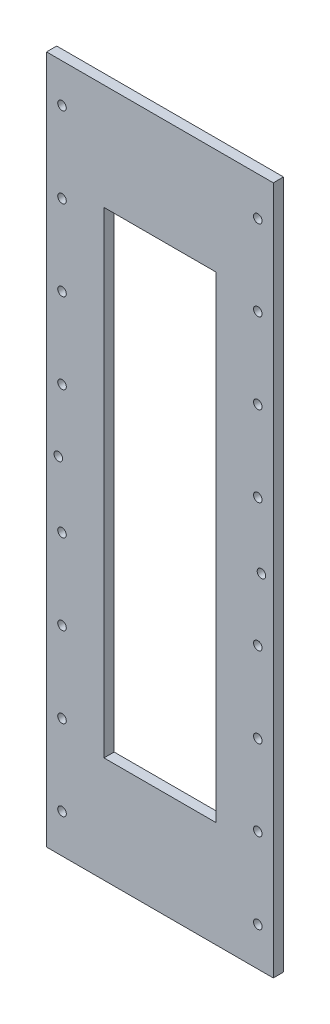
SolidWorks part; units mm, degrees
ref_plane "Front Plane" through (0, 0, 0) normal (0, 0, 1) x (1, 0, 0)
ref_plane "Top Plane" through (0, 0, 0) normal (0, 1, 0) x (1, 0, 0)
ref_plane "Right Plane" through (0, 0, 0) normal (1, 0, 0) x (0, 0, -1)
sketch "Sketch1" plane through (0, 0, 0.1) normal (0, 0, 1) x (1, 0, 0)
  line L0 (-40.45, -31.4857) -> (-40.45, -150) construction
  line L1 (-27.45, 117) -> (27.45, 117)
  line L2 (-30.45, 120) -> (30.45, 120)
  line L3 (-30.45, 120) -> (-30.45, -120)
  line L4 (-30.45, -120) -> (30.45, -120)
  line L5 (30.45, 120) -> (30.45, -120)
  line L6 (27.45, 117) -> (27.45, -117)
  line L7 (-27.45, -117) -> (27.45, -117)
  line L8 (0, -161.5) -> (0, -169)
  line L9 (-55.65, 169) -> (55.65, 169)
  line L10 (-55.65, 169) -> (-55.65, -169)
  line L11 (-55.65, -169) -> (55.65, -169)
  line L12 (55.65, 169) -> (55.65, -169)
  line L14 (67.25, -161.5) -> (-67.25, -161.5) construction
  line L15 (-27.45, 117) -> (-27.45, -117)
  line L16 (0, 169) -> (0, 161.5) construction
  line L19 (0, 169) -> (0, 176.5) construction
  line L22 (82.25, 176.5) -> (-82.25, 176.5) construction
  line L23 (-67.25, 161.5) -> (67.25, 161.5) construction
  line L32 (0, -176.5) -> (0, -169)
  line L34 (-82.25, -176.5) -> (82.25, -176.5) construction
  circle A0 centre (-48.05, -150) radius 2.1 construction
  circle A1 centre (48.05, -150) radius 2.1 construction
  circle A2 centre (49.85, 0) radius 2.1
  circle A3 centre (48.05, -70.9904) radius 2.1
  circle A4 centre (48.05, -110.4952) radius 2.1
  circle A5 centre (48.05, -150) radius 2.1
  circle A6 centre (-48.05, -150) radius 2.1
  circle A7 centre (-48.05, -110.4952) radius 2.1
  circle A8 centre (-48.05, -70.9904) radius 2.1
  circle A9 centre (-48.05, 150) radius 2.1 construction
  circle A23 centre (-48.05, 150) radius 2.1
  circle A24 centre (48.05, 150) radius 2.1
  circle A25 centre (48.05, 110.4952) radius 2.1
  circle A26 centre (-48.05, 110.4952) radius 2.1
  circle A27 centre (-48.05, 70.9904) radius 2.1
  circle A28 centre (-48.05, 31.4857) radius 2.1
  circle A29 centre (48.05, 70.9904) radius 2.1
  circle A30 centre (48.05, 31.4857) radius 2.1
  circle A31 centre (-49.85, 0) radius 2.1
  circle A64 centre (-48.05, -31.4857) radius 2.1
  circle A65 centre (48.05, -31.4857) radius 2.1
  line M30 (10.45, -45) -> (30.45, -45)
  line M31 (30.45, -45) -> (30.45, -103)
  line M32 (30.45, -103) -> (10.45, -103)
  line M33 (-10.45, -103) -> (-30.45, -103)
  line M34 (-30.45, -103) -> (-30.45, -45)
  line M35 (-30.45, -45) -> (-10.45, -45)
  line M38 (-10.45, 45) -> (-30.45, 45)
  line M39 (-30.45, 45) -> (-30.45, 103)
  line M40 (-30.45, 103) -> (-10.45, 103)
  line M41 (10.45, 103) -> (30.45, 103)
  line M42 (30.45, 103) -> (30.45, 45)
  line M43 (30.45, 45) -> (10.45, 45)
  arc M45 (-45.6346, -16.16) -> (-41.3067, -23.1285) centre (-50.75, -24.1652) cw
  arc M46 (-41.3067, -23.1285) -> (-45.45, -31.4857) centre (-34.95, -31.4857) ccw
  line M47 (-45.45, -31.4857) -> (-45.45, -150)
  arc M48 (-45.45, -150) -> (-34.95, -160.5) centre (-34.95, -150) ccw
  line M49 (-34.95, -160.5) -> (34.95, -160.5)
  arc M50 (34.95, -160.5) -> (45.45, -150) centre (34.95, -150) ccw
  line M51 (45.45, -150) -> (45.45, -31.4857)
  arc M52 (45.45, -31.4857) -> (41.3067, -23.1285) centre (34.95, -31.4857) ccw
  arc M53 (41.3067, -23.1285) -> (45.6346, -16.16) centre (50.75, -24.1652) cw
  arc M54 (45.6346, -16.16) -> (47.25, -13.2107) centre (43.75, -13.2107) ccw
  line M55 (47.25, -13.2107) -> (47.25, 13.2107)
  arc M56 (47.25, 13.2107) -> (45.6346, 16.16) centre (43.75, 13.2107) ccw
  arc M57 (45.6346, 16.16) -> (41.3067, 23.1285) centre (50.75, 24.1652) cw
  arc M58 (41.3067, 23.1285) -> (45.45, 31.4857) centre (34.95, 31.4857) ccw
  line M59 (45.45, 31.4857) -> (45.45, 150)
  arc M60 (45.45, 150) -> (34.95, 160.5) centre (34.95, 150) ccw
  line M61 (34.95, 160.5) -> (-34.95, 160.5)
  arc M62 (-34.95, 160.5) -> (-45.45, 150) centre (-34.95, 150) ccw
  line M63 (-45.45, 150) -> (-45.45, 31.4857)
  arc M64 (-45.45, 31.4857) -> (-41.3067, 23.1285) centre (-34.95, 31.4857) ccw
  arc M65 (-41.3067, 23.1285) -> (-45.6346, 16.16) centre (-50.75, 24.1652) cw
  arc M66 (-45.6346, 16.16) -> (-47.25, 13.2107) centre (-43.75, 13.2107) ccw
  line M67 (-47.25, 13.2107) -> (-47.25, -13.2107)
  arc M68 (-47.25, -13.2107) -> (-45.6346, -16.16) centre (-43.75, -13.2107) ccw
  dimension "D1" = 7.6
  dimension "D2" = 7.6
  dimension "D3" = 7.6
  dimension "D5" = 180
  dimension "D4" = 3
sketch "Sketch2" plane through (0, 0, 0.1) normal (0, 0, 1) x (1, 0, 0)
  line L12 (45.45, 31.4857) -> (45.45, 150)
  line L14 (45.45, 31.4857) -> (45.45, 150)
  line L16 (-45.45, -31.4857) -> (-45.45, -150)
  line L17 (-34.95, -160.5) -> (34.95, -160.5)
  line L18 (45.45, -150) -> (45.45, -31.4857)
  line L19 (47.25, -13.2107) -> (47.25, 13.2107)
  line L24 (-45.45, -31.4857) -> (-45.45, -150)
  line L25 (-34.95, -160.5) -> (34.95, -160.5)
  line L26 (45.45, -150) -> (45.45, -31.4857)
  line L27 (47.25, -13.2107) -> (47.25, 13.2107)
  line L38 (34.95, 160.5) -> (-34.95, 160.5)
  line L39 (34.95, 160.5) -> (-34.95, 160.5)
  line L40 (-45.45, 150) -> (-45.45, 31.4857)
  line L41 (-45.45, 150) -> (-45.45, 31.4857)
  line L42 (-47.25, 13.2107) -> (-47.25, -13.2107)
  line L43 (-47.25, 13.2107) -> (-47.25, -13.2107)
  line L44 (-42.25, 12.4178) -> (-42.25, -12.4178)
  line L45 (-42.25, 12.4178) -> (-42.25, -12.4178)
  line L46 (-40.45, -31.4857) -> (-40.45, -150)
  line L47 (-40.45, -31.4857) -> (-40.45, -150)
  line L56 (-34.95, -155.5) -> (34.95, -155.5)
  line L57 (-34.95, -155.5) -> (34.95, -155.5)
  line L58 (40.45, -150) -> (40.45, -31.4857)
  line L59 (40.45, -150) -> (40.45, -31.4857)
  line L60 (42.25, -12.4178) -> (42.25, 12.4178)
  line L61 (42.25, -12.4178) -> (42.25, 12.4178)
  line L62 (40.45, 31.4857) -> (40.45, 150)
  line L63 (40.45, 31.4857) -> (40.45, 150)
  line L64 (34.95, 155.5) -> (-34.95, 155.5)
  line L65 (34.95, 155.5) -> (-34.95, 155.5)
  line L66 (-40.45, 150) -> (-40.45, 31.4857)
  line L67 (-40.45, 150) -> (-40.45, 31.4857)
  arc A9 (-42.25, 12.4178) -> (-36.3903, 26.1776) centre (-50.75, 24.1652) ccw
  arc A32 (-41.3067, -23.1285) -> (-45.6346, -16.16) centre (-50.75, -24.1652) ccw
  arc A33 (-41.3067, -23.1285) -> (-45.45, -31.4857) centre (-34.95, -31.4857) ccw
  arc A34 (-45.45, -150) -> (-34.95, -160.5) centre (-34.95, -150) ccw
  arc A35 (34.95, -160.5) -> (45.45, -150) centre (34.95, -150) ccw
  arc A36 (45.45, -31.4857) -> (41.3067, -23.1285) centre (34.95, -31.4857) ccw
  arc A37 (45.6346, -16.16) -> (41.3067, -23.1285) centre (50.75, -24.1652) ccw
  arc A38 (45.6346, -16.16) -> (47.25, -13.2107) centre (43.75, -13.2107) ccw
  arc A45 (-42.25, 12.4178) -> (-36.3903, 26.1776) centre (-50.75, 24.1652) ccw
  arc A46 (-36.3903, -26.1776) -> (-42.25, -12.4178) centre (-50.75, -24.1652) ccw
  arc A47 (-47.25, -13.2107) -> (-45.6346, -16.16) centre (-43.75, -13.2107) ccw
  arc A48 (-41.3067, -23.1285) -> (-45.6346, -16.16) centre (-50.75, -24.1652) ccw
  arc A49 (-41.3067, -23.1285) -> (-45.45, -31.4857) centre (-34.95, -31.4857) ccw
  arc A50 (-45.45, -150) -> (-34.95, -160.5) centre (-34.95, -150) ccw
  arc A51 (34.95, -160.5) -> (45.45, -150) centre (34.95, -150) ccw
  arc A52 (45.45, -31.4857) -> (41.3067, -23.1285) centre (34.95, -31.4857) ccw
  arc A53 (45.6346, -16.16) -> (41.3067, -23.1285) centre (50.75, -24.1652) ccw
  arc A54 (45.6346, -16.16) -> (47.25, -13.2107) centre (43.75, -13.2107) ccw
  arc A63 (-47.25, -13.2107) -> (-45.6346, -16.16) centre (-43.75, -13.2107) ccw
  arc A64 (-36.3903, -26.1776) -> (-42.25, -12.4178) centre (-50.75, -24.1652) ccw
  arc A65 (-36.3903, -26.1776) -> (-40.45, -31.4857) centre (-34.95, -31.4857) ccw
  arc A66 (47.25, 13.2107) -> (45.6346, 16.16) centre (43.75, 13.2107) ccw
  arc A67 (47.25, 13.2107) -> (45.6346, 16.16) centre (43.75, 13.2107) ccw
  arc A68 (41.3067, 23.1285) -> (45.6346, 16.16) centre (50.75, 24.1652) ccw
  arc A69 (41.3067, 23.1285) -> (45.6346, 16.16) centre (50.75, 24.1652) ccw
  arc A70 (41.3067, 23.1285) -> (45.45, 31.4857) centre (34.95, 31.4857) ccw
  arc A71 (41.3067, 23.1285) -> (45.45, 31.4857) centre (34.95, 31.4857) ccw
  arc A72 (45.45, 150) -> (34.95, 160.5) centre (34.95, 150) ccw
  arc A73 (45.45, 150) -> (34.95, 160.5) centre (34.95, 150) ccw
  arc A74 (-34.95, 160.5) -> (-45.45, 150) centre (-34.95, 150) ccw
  arc A75 (-34.95, 160.5) -> (-45.45, 150) centre (-34.95, 150) ccw
  arc A76 (-45.45, 31.4857) -> (-41.3067, 23.1285) centre (-34.95, 31.4857) ccw
  arc A77 (-45.45, 31.4857) -> (-41.3067, 23.1285) centre (-34.95, 31.4857) ccw
  arc A78 (-45.6346, 16.16) -> (-41.3067, 23.1285) centre (-50.75, 24.1652) ccw
  arc A79 (-45.6346, 16.16) -> (-41.3067, 23.1285) centre (-50.75, 24.1652) ccw
  arc A80 (-45.6346, 16.16) -> (-47.25, 13.2107) centre (-43.75, 13.2107) ccw
  arc A81 (-45.6346, 16.16) -> (-47.25, 13.2107) centre (-43.75, 13.2107) ccw
  arc A82 (-36.3903, -26.1776) -> (-40.45, -31.4857) centre (-34.95, -31.4857) ccw
  arc A83 (-40.45, -150) -> (-34.95, -155.5) centre (-34.95, -150) ccw
  arc A96 (-40.45, -150) -> (-34.95, -155.5) centre (-34.95, -150) ccw
  arc A97 (34.95, -155.5) -> (40.45, -150) centre (34.95, -150) ccw
  arc A98 (34.95, -155.5) -> (40.45, -150) centre (34.95, -150) ccw
  arc A99 (40.45, -31.4857) -> (36.3903, -26.1776) centre (34.95, -31.4857) ccw
  arc A100 (40.45, -31.4857) -> (36.3903, -26.1776) centre (34.95, -31.4857) ccw
  arc A101 (42.25, -12.4178) -> (36.3903, -26.1776) centre (50.75, -24.1652) ccw
  arc A102 (42.25, -12.4178) -> (36.3903, -26.1776) centre (50.75, -24.1652) ccw
  arc A103 (36.3903, 26.1776) -> (42.25, 12.4178) centre (50.75, 24.1652) ccw
  arc A104 (36.3903, 26.1776) -> (42.25, 12.4178) centre (50.75, 24.1652) ccw
  arc A105 (36.3903, 26.1776) -> (40.45, 31.4857) centre (34.95, 31.4857) ccw
  arc A106 (36.3903, 26.1776) -> (40.45, 31.4857) centre (34.95, 31.4857) ccw
  arc A107 (40.45, 150) -> (34.95, 155.5) centre (34.95, 150) ccw
  arc A108 (40.45, 150) -> (34.95, 155.5) centre (34.95, 150) ccw
  arc A109 (-34.95, 155.5) -> (-40.45, 150) centre (-34.95, 150) ccw
  arc A110 (-34.95, 155.5) -> (-40.45, 150) centre (-34.95, 150) ccw
  arc A111 (-40.45, 31.4857) -> (-36.3903, 26.1776) centre (-34.95, 31.4857) ccw
  arc A112 (-40.45, 31.4857) -> (-36.3903, 26.1776) centre (-34.95, 31.4857) ccw
  arc M61 (-45.6346, -16.16) -> (-41.3067, -23.1285) centre (-50.75, -24.1652) cw
  arc M62 (-41.3067, -23.1285) -> (-45.45, -31.4857) centre (-34.95, -31.4857) ccw
  line M63 (-45.45, -31.4857) -> (-45.45, -150)
  arc M64 (-45.45, -150) -> (-34.95, -160.5) centre (-34.95, -150) ccw
  line M65 (-34.95, -160.5) -> (34.95, -160.5)
  arc M66 (34.95, -160.5) -> (45.45, -150) centre (34.95, -150) ccw
  line M67 (45.45, -150) -> (45.45, -31.4857)
  arc M68 (45.45, -31.4857) -> (41.3067, -23.1285) centre (34.95, -31.4857) ccw
  arc M69 (41.3067, -23.1285) -> (45.6346, -16.16) centre (50.75, -24.1652) cw
  arc M70 (45.6346, -16.16) -> (47.25, -13.2107) centre (43.75, -13.2107) ccw
  line M71 (47.25, -13.2107) -> (47.25, 13.2107)
  arc M72 (47.25, 13.2107) -> (45.6346, 16.16) centre (43.75, 13.2107) ccw
  arc M73 (45.6346, 16.16) -> (41.3067, 23.1285) centre (50.75, 24.1652) cw
  arc M74 (41.3067, 23.1285) -> (45.45, 31.4857) centre (34.95, 31.4857) ccw
  line M75 (45.45, 31.4857) -> (45.45, 150)
  arc M76 (45.45, 150) -> (34.95, 160.5) centre (34.95, 150) ccw
  line M77 (34.95, 160.5) -> (-34.95, 160.5)
  arc M78 (-34.95, 160.5) -> (-45.45, 150) centre (-34.95, 150) ccw
  line M79 (-45.45, 150) -> (-45.45, 31.4857)
  arc M80 (-45.45, 31.4857) -> (-41.3067, 23.1285) centre (-34.95, 31.4857) ccw
  arc M81 (-41.3067, 23.1285) -> (-45.6346, 16.16) centre (-50.75, 24.1652) cw
  arc M82 (-45.6346, 16.16) -> (-47.25, 13.2107) centre (-43.75, 13.2107) ccw
  line M83 (-47.25, 13.2107) -> (-47.25, -13.2107)
  arc M84 (-47.25, -13.2107) -> (-45.6346, -16.16) centre (-43.75, -13.2107) ccw
  dimension "D1" = 0
  dimension "D2" = 0
extrude "Boss-Extrude1" add sketch "Sketch2" along normal up to surface (6 mm away) contours A112 L67 A110 L65 A108 L63 A106 A104 L61 A102 A100 L59 A98 L57 A96 L47 A82 A64 L45 A45 M84 M61 M62 M63 M64 M65 M66 M67 M68 M69 M70 M71 M72 M73 M74 M75 M76 M77 M78 M79 M80 M81 M82 M83
extrude "Boss-Extrude2" add sketch "Sketch1" along normal blind 5 from surface at 6 contours L2 L5 L4 L3 M68 M45 M46 M47 M48 M49 M50 M51 M52 M53 M54 M55 M56 M57 M58 M59 M60 M61 M62 M63 M64 M65 M66 M67 M42 M31 M34 M39 | L12 L9 L11 A65 A30 A29 A25 A24 A5 A4 A3 A2 M60 M59 M58 M57 M56 M55 M54 M53 M52 M51 M50 | L10 L11 L9 A64 A31 A28 A27 A26 A23 A8 A7 A6 M48 M47 M46 M45 M68 M67 M66 M65 M64 M63 M62 | L15 L1 L6 L5 L2 L3 M41 M40 | L15 M40 M39 M38 | L6 M41 M43 M42 | L6 L5 M43 M30 | L15 L3 M38 M35 | L15 M35 M34 M33 | L15 L3 L4 L5 L6 L7 M33 M32 | L6 M30 M32 M31
sketch "Sketch3" plane through (0, 0, 6.1) normal (0, 0, -1) x (-1, 0, 0)
  line L0 (-55.65, 0) -> (-46.25, 0)
  line L1 (-55.65, 169) -> (-55.65, -169) construction
  line L2 (-46.25, 0) -> (-51.25, 5)
  line L3 (-51.25, 5) -> (-31.85, 5)
  line L4 (-31.85, 5) -> (-36.85, 0)
  line L5 (-36.85, 0) -> (-27.45, 0)
  line L6 (-27.45, 117) -> (-27.45, -117) construction
  line L7 (0, 0) -> (0, 22.2836) construction
  line L8 (36.85, 0) -> (27.45, 0)
  line L9 (-54.525, 5) -> (-79.675, 5) construction
  line L10 (-46.25, 0) -> (-36.85, 0) construction
  line L11 (31.85, 5) -> (36.85, 0)
  line L12 (51.25, 5) -> (31.85, 5)
  line L13 (46.25, 0) -> (51.25, 5)
  line L14 (55.65, 0) -> (46.25, 0)
  dimension "D1" = 45
equation "\"D2@Sketch1\"=\"D1@Sketch1\""
equation "\"D3@Sketch1\"=\"D2@Sketch1\""
